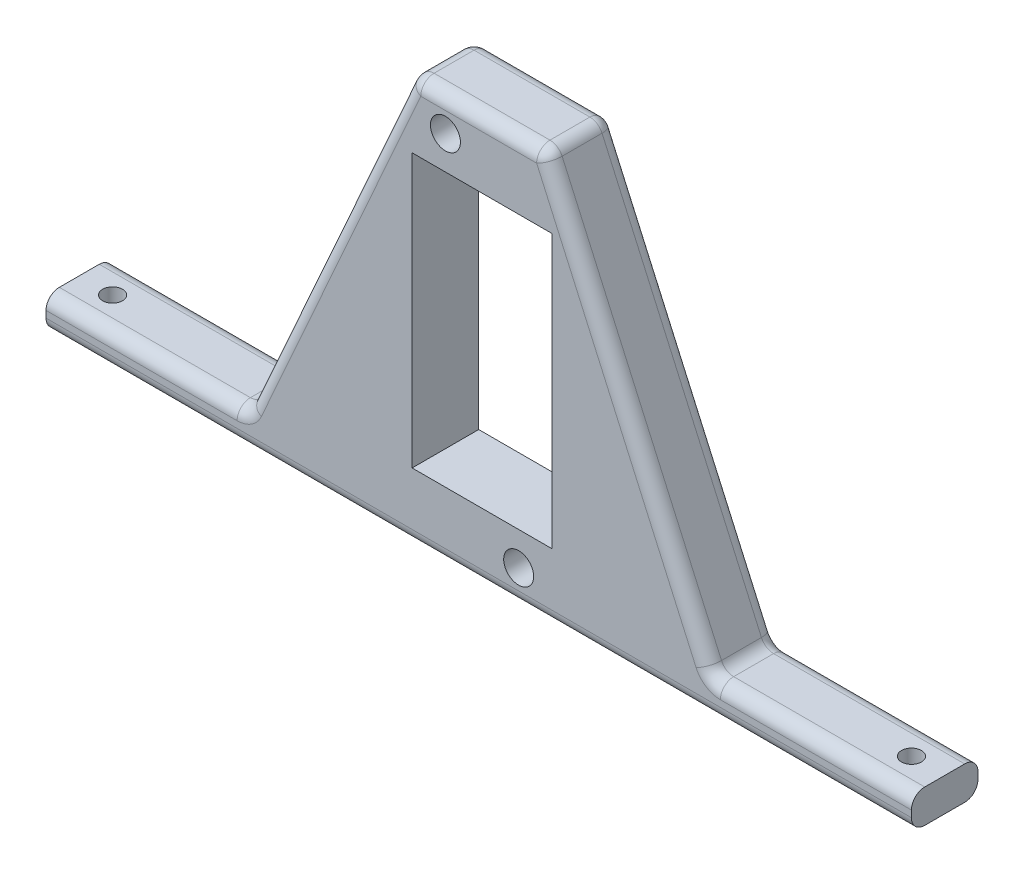
SolidWorks part; units mm, degrees
ref_plane "Front Plane" through (0, 0, 0) normal (0, 0, 1) x (1, 0, 0)
ref_plane "Top Plane" through (0, 0, 0) normal (0, 1, 0) x (1, 0, 0)
ref_plane "Right Plane" through (0, 0, 0) normal (1, 0, 0) x (0, 0, -1)
sketch "Sketch1" plane through (0, 0, 0) normal (0, 0, 1) x (1, 0, 0)
  line L0 (-36.9051, 13.198) -> (-36.9051, -27.802)
  line L1 (-36.9051, -27.802) -> (-15.9051, -27.802)
  line L2 (-15.9051, -27.802) -> (-15.9051, 13.198)
  line L3 (-15.9051, 13.198) -> (-36.9051, 13.198)
  line L4 (-16.9051, 23.198) -> (-36.9051, 23.198)
  line L5 (-36.9051, 23.198) -> (-61.9051, -32.802)
  line L6 (-61.9051, -32.802) -> (-91.9051, -32.802)
  line L7 (-91.9051, -32.802) -> (-91.9051, -37.802)
  line L8 (-91.9051, -37.802) -> (38.0949, -37.802)
  line L9 (38.0949, -37.802) -> (38.0949, -32.802)
  line L10 (38.0949, -32.802) -> (8.0949, -32.802)
  line L11 (8.0949, -32.802) -> (-16.9051, 23.198)
  circle A0 centre (-31.9051, 18.198) radius 2.25
  circle A1 centre (-20.9051, -32.802) radius 2.25
  dimension "D14" = 4.5
  dimension "D15" = 4.5
  dimension "D16" = 5
  dimension "D17" = 5
  dimension "D18" = 5
  dimension "D19" = 5
  dimension "D1" = 21
  dimension "D2" = 41
  dimension "D3" = 41
  dimension "D4" = 10
  dimension "D5" = 5
  dimension "D6" = 5
  dimension "D7" = 30
  dimension "D8" = 30
  dimension "D9" = 25
  dimension "D10" = 25
  dimension "D11" = 20
  dimension "D12" = 0
  dimension "D13" = 10
extrude "Boss-Extrude1" add sketch "Sketch1" along normal blind 10 contours L10 L11 L4 L5 L6 L7 L8 L9 A1 A0 L3 L2 L1 L0 | A0 | A1 region at (-5.7164, -5.3874, 0) region at (-31.9051, 18.198, 0) region at (-20.9051, -32.802, 0)
extrude "Cut-Extrude1" cut sketch "Sketch1<3>" along normal blind 10 contours A0 | A1 region at (-31.9051, 18.198, 0) region at (-20.9051, -32.802, 0)
sketch "Sketch1<3>" plane through (0, 0, 0) normal (0, 0, 1) x (1, 0, 0) same geometry as "Sketch1"
sketch "Sketch2" plane through (0, -32.802, 0) normal (0, 1, 0) x (1, 0, 0)
  line L0 (38.0949, -10) -> (38.0949, 0) construction
  line L1 (38.0949, -10) -> (8.0949, -10) construction
  line L2 (-91.9051, -10) -> (-91.9051, 0) construction
  line L3 (-61.9051, -10) -> (-91.9051, -10) construction
  circle A0 centre (33.0949, -5) radius 1.5
  circle A1 centre (-86.9051, -5) radius 1.5
  dimension "D1" = 3
  dimension "D2" = 3
  dimension "D3" = 5
  dimension "D4" = 5
  dimension "D5" = 5
  dimension "D6" = 5
extrude "Cut-Extrude2" cut sketch "Sketch2" against normal blind 5
fillet "Fillet1" radius 2 4 edges at (-61.9051, -32.802, 5) (8.0949, -32.802, 5) (-36.9051, 23.198, 5) (-16.9051, 23.198, 5)
fillet "Fillet2" radius 2 20 edges at (23.7436, -32.802, 0) (8.3038, -32.4799, 0) (-77.5538, -32.802, 0) (-62.1141, -32.4799, 0) (-49.4051, -4.802, 0) (-36.6962, 22.8759, 0) (-26.9051, 23.198, 0) (-17.1141, 22.8759, 0) (23.7436, -32.802, 10) (8.3038, -32.4799, 10) (-77.5538, -32.802, 10) (-62.1141, -32.4799, 10) (-49.4051, -4.802, 10) (-36.6962, 22.8759, 10) (-26.9051, 23.198, 10) (-17.1141, 22.8759, 10) (-26.9051, -37.802, 10) (-26.9051, -37.802, 0) (-4.4051, -4.802, 0) (-4.4051, -4.802, 10)
